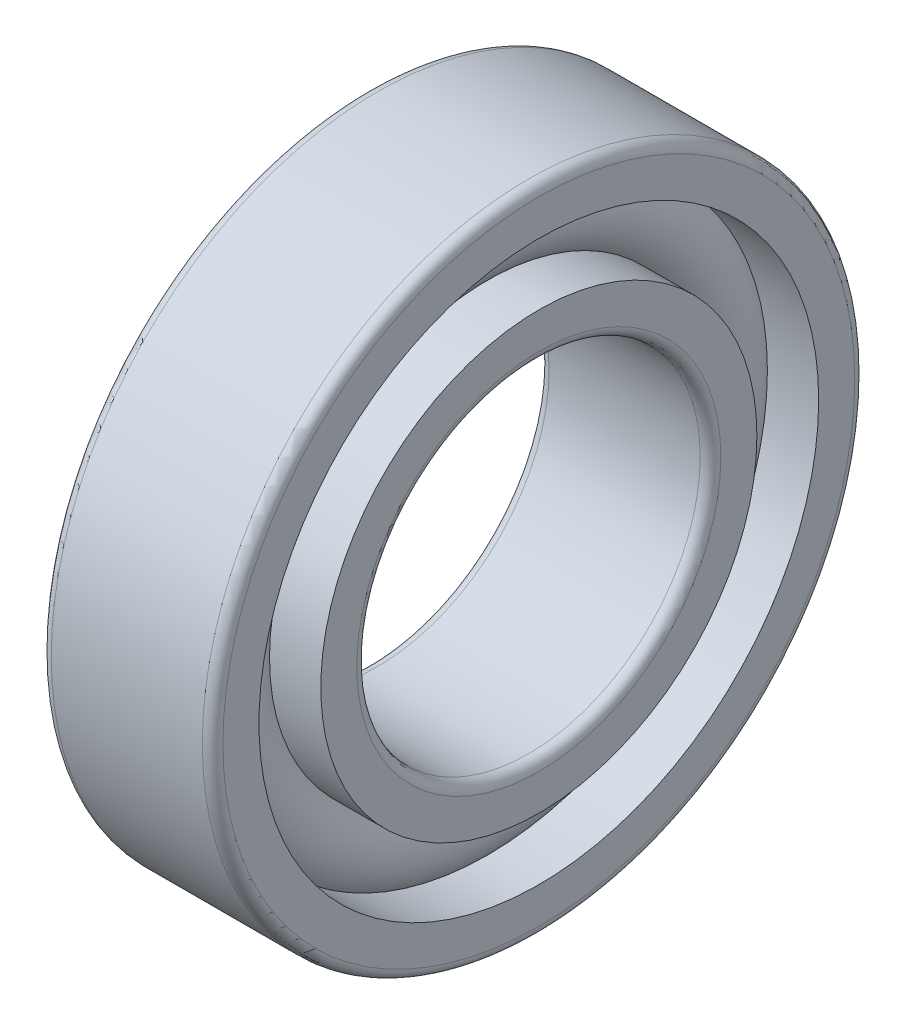
SolidWorks part; units mm, degrees
ref_plane "Plane1" through (0, 0, 0) normal (0, 0, 1) x (1, 0, 0)
ref_plane "Plane2" through (0, 0, 0) normal (0, 1, 0) x (1, 0, 0)
ref_plane "Plane3" through (0, 0, 0) normal (1, 0, 0) x (0, 0, -1)
other "Configuration Table"
sketch "Clipboard" plane through (0, 0, 0) normal (0, 0, 1) x (1, 0, 0)
  line L0 (-10, 0) -> (10, 0) construction
  line L1 (0, 0) -> (22.3471, -0.7804)
  line L2 (0, 0) -> (7.2456, 0.253)
  line L3 (0, 0) -> (22.3471, -0.7804)
  line L4 (0, 0) -> (-22.3573, -0.3902)
  dimension "BallCLRad" = 7.25
sketch "CagSpiSke" plane through (0, 0, 0) normal (0, 0, 1) x (1, 0, 0)
  line L0 (0.135, 7.025) -> (0.135, 7.475)
  line L1 (0.135, 7.475) -> (-0.135, 7.475)
  line L2 (-0.135, 7.475) -> (-0.135, 7.025)
  line L3 (-0.135, 7.025) -> (0.135, 7.025)
  line L4 (-20.6375, 0) -> (20.6375, 0) construction
  line L5 (0, 0) -> (0, 23.7692) construction
  dimension "OD" = 14.95
  dimension "ID" = 14.05
revolve "CageSpine" add sketch "CagSpiSke" angle 0.001 about L4 reverse direction yes
ref_axis "Axis1" through (-50, 0, 0) along (1, 0, 0)
sketch "CagBalSke" plane through (0, 0, 0) normal (0, 0, 1) x (1, 0, 0)
  line L0 (-1.485, 7.25) -> (1.485, 7.25)
  line L1 (-1.905, 7.25) -> (1.905, 7.25) construction
  line L2 (-10, 0) -> (10, 0) construction
  line L3 (0, 0) -> (0, 24) construction
  arc A0 (1.485, 7.25) -> (-1.485, 7.25) centre (0, 7.25) cw
  dimension "BallCLRad" = 7.25
revolve "CageBall" [suppressed] add sketch "CagBalSke" angle 360 about L1 reverse direction yes
pattern_circular "CageBalls" [suppressed] count 2 every 180 about axis through (-50, 0, 0) along (1, 0, 0)
sketch "CagTrmODSke" plane through (0, 0, 0) normal (0, 0, 1) x (1, 0, 0)
  line L0 (1.486, 7.475) -> (1.486, 8.736)
  line L1 (1.486, 8.736) -> (-1.486, 8.736)
  line L2 (-1.486, 8.736) -> (-1.486, 7.475)
  line L3 (-1.486, 7.475) -> (1.486, 7.475)
  line L4 (-20.6375, 0) -> (20.6375, 0) construction
  line L5 (0, 0) -> (0, 25) construction
  dimension "Width" = 2.972
  dimension "ID" = 14.95
  dimension "OD" = 17.472
revolve "CageTrimOD" [suppressed] cut sketch "CagTrmODSke" angle 360 about L4 reverse direction yes
sketch "CagTrmIDSke" plane through (0, 0, 0) normal (0, 0, 1) x (1, 0, 0)
  line L0 (1.486, 5.766) -> (1.486, 7.025)
  line L1 (1.486, 7.025) -> (-1.486, 7.025)
  line L2 (-1.486, 7.025) -> (-1.486, 5.766)
  line L3 (-1.486, 5.766) -> (1.486, 5.766)
  line L4 (-20.6375, 0) -> (20.6375, 0) construction
  line L5 (0, 0) -> (0, 25) construction
  dimension "Width" = 2.972
  dimension "ID" = 11.532
  dimension "OD" = 14.05
revolve "CageTrimID" [suppressed] cut sketch "CagTrmIDSke" angle 360 about L4 reverse direction yes
sketch "BalSimSke" plane through (0, 0, 0) normal (0, 0, 1) x (1, 0, 0)
  line L0 (-10, 0) -> (10, 0) construction
  line L1 (-10, 7.25) -> (10, 7.25) construction
  line L2 (0, 0) -> (0, 23) construction
  circle A0 centre (0, 7.25) radius 1.35
  dimension "BallCLRad" = 7.25
  dimension "Ball_diameter" = 2.7
revolve "BallsSimplified" add sketch "BalSimSke" angle 360 about L0
sketch "BalDetSke" plane through (0, 0, 0) normal (0, 0, 1) x (1, 0, 0)
  line L0 (-1.35, 7.25) -> (1.35, 7.25)
  line L1 (-1.905, 7.25) -> (1.905, 7.25) construction
  line L2 (0, 0) -> (0, 25) construction
  arc A0 (1.35, 7.25) -> (-1.35, 7.25) centre (0, 7.25) cw
  dimension "BallCLRad" = 7.25
  dimension "Ball_diameter" = 2.7
revolve "BallDetailed" [suppressed] add sketch "BalDetSke" angle 360 about L1 reverse direction yes
sketch "InnRacSke" plane through (0, 0, 0) normal (0, 0, 1) x (1, 0, 0)
  line L0 (-0.9724, 6.35) -> (-2.5, 6.35)
  line L1 (-2.5, 6.35) -> (-2.5, 5.3)
  line L2 (-2.2, 5) -> (2.2, 5)
  line L3 (2.5, 5.3) -> (2.5, 6.35)
  line L4 (2.5, 6.35) -> (0.9724, 6.35)
  line L5 (-20.6375, 0) -> (20.6375, 0) construction
  line L6 (0, 0) -> (0, 30) construction
  arc A0 (-2.5, 5.3) -> (-2.2, 5) centre (-2.2, 5.3) ccw
  arc A1 (2.2, 5) -> (2.5, 5.3) centre (2.2, 5.3) ccw
  arc A2 (0.9724, 6.35) -> (-0.9724, 6.35) centre (0, 7.25) cw
  dimension "BallCLRad" = 7.25
  dimension "Fillet_radius" = 0.3
  dimension "Ball_diameter" = 2.65
  dimension "ID" = 10
  dimension "OD" = 12.7
  dimension "Width" = 5
revolve "InnerRace" add sketch "InnRacSke" angle 360 about L5 reverse direction yes
sketch "OutRacSke" plane through (0, 0, 0) normal (0, 0, 1) x (1, 0, 0)
  line L0 (-0.9724, 8.15) -> (-2.5, 8.15)
  line L1 (-2.5, 8.15) -> (-2.5, 9.2)
  line L2 (-2.2, 9.5) -> (2.2, 9.5)
  line L3 (2.5, 9.2) -> (2.5, 8.15)
  line L4 (2.5, 8.15) -> (0.9724, 8.15)
  line L5 (-20.6375, 0) -> (20.6375, 0) construction
  line L6 (0, 0) -> (0, 30) construction
  arc A0 (-2.5, 9.2) -> (-2.2, 9.5) centre (-2.2, 9.2) cw
  arc A1 (2.2, 9.5) -> (2.5, 9.2) centre (2.2, 9.2) cw
  arc A2 (0.9724, 8.15) -> (-0.9724, 8.15) centre (0, 7.25) ccw
  dimension "BallCLRad" = 7.25
  dimension "Fillet_radius" = 0.3
  dimension "Ball_diameter" = 2.65
  dimension "Width" = 5
revolve "OuterRace" add sketch "OutRacSke" angle 360 about L5 reverse direction yes
pattern_circular "BallsDetailed" [suppressed] count 2 every 180 about axis through (-50, 0, 0) along (1, 0, 0)
equation "\"BallCLRad@Clipboard\" = ( \"OD@OutRacSke\" + \"ID@InnRacSke\" ) / 4"
equation "\"BallCLRad@BalSimSke\" = \"BallCLRad@Clipboard\""
equation "\"BallCLRad@BalDetSke\" = \"BallCLRad@Clipboard\""
equation "\"BallCLRad@InnRacSke\" = \"BallCLRad@Clipboard\""
equation "\"BallCLRad@OutRacSke\" = \"BallCLRad@Clipboard\""
equation "\"Ball_diameter@InnRacSke\" = \"Ball_diameter@BalDetSke\" - 0.05"
equation "\"Ball_diameter@OutRacSke\" = \"Ball_diameter@BalDetSke\" - 0.05"
equation "\"Ball_diameter@BalSimSke\" = \"Ball_diameter@BalDetSke\""
equation "\"Width@OutRacSke\" = \"Width@InnRacSke\""
equation "\"Fillet_radius@OutRacSke\" = \"Fillet_radius@InnRacSke\""
equation "\"Max_count@Clipboard\" = int( 3.14159265 / atn(( \"Ball_diameter@BalDetSke\" / 2) / sqr( \"BallCLRad@Clipboard\"  *  \"BallCLRad@Clipboard\" - ( \"Ball_diameter@BalDetSke\" / 2) *  ( \"Ball_diameter@BalDetSke\" / 2))))"
equation "\"Max_count@Clipboard\" = ((sgn( \"Max_count@Clipboard\" - \"Count@Clipboard\" )-1)*( \"Max_count@Clipboard\" - \"Count@Clipboard\" ))/-2+ \"Count@Clipboard\""
equation "\"Count@BallsDetailed\" = int( \"Show_count@Clipboard\" ) "
equation "\"Count@BallsDetailed\" = ((sgn( \"Count@BallsDetailed\" - \"Max_count@Clipboard\" )-1)*( \"Count@BallsDetailed\" - \"Max_count@Clipboard\" ))/-2+ \"Max_count@Clipboard\""
equation "\"Count@BallsDetailed\" = ((sgn( \"Count@BallsDetailed\" - \"Min_count@Clipboard\" )+1)*( \"Count@BallsDetailed\" - \"Min_count@Clipboard\"))/2 +\"Min_count@Clipboard\""
equation "\"Angle@BallsDetailed\" = 360.0 / \"Max_count@Clipboard\""
equation "\"BallCLRad@CagBalSke\" = \"BallCLRad@Clipboard\""
equation "\"Count@CageBalls\" = \"Count@BallsDetailed\""
equation "\"Angle@CageBalls\" = \"Angle@BallsDetailed\""
equation "\"Angle@CageSpine\" =  \"Angle@CageBalls\" * ( \"Count@CageBalls\" -1 + int( \"Count@CageBalls\" / \"Max_count@Clipboard\" ) )  + 0.001 -  int( \"Count@CageBalls\" / \"Max_count@Clipboard\" ) * 0.001"
equation "\"Angle@CageSpine\" =  \"Angle@CageSpine\" * int( \"Min_count@Clipboard\" / 2) + int(1 / \"Min_count@Clipboard\")  * 0.001"
equation "\"CageWallOD@CagBalSke\" =  \"Ball_diameter@BalDetSke\" * 1.1"
equation "\"Thickness@CagSpiSke\" =  \"Ball_diameter@BalDetSke\" * 0.1"
equation "\"OD@CagTrmODSke\" = \"BallCLRad@Clipboard\" * 2 + \"CageWallOD@CagBalSke\" + 0.002"
equation "\"ID@CagTrmODSke\" = \"BallCLRad@Clipboard\" * 2 + \"Ball_diameter@BalDetSke\" / 6"
equation "\"OD@CagTrmIDSke\" = \"BallCLRad@Clipboard\" * 2 - \"Ball_diameter@BalDetSke\" / 6"
equation "\"ID@CagTrmIDSke\" = \"BallCLRad@Clipboard\" * 2 - \"CageWallOD@CagBalSke\" + 0.002"
equation "\"OD@CagSpiSke\" = \"ID@CagTrmODSke\""
equation "\"ID@CagSpiSke\" = \"OD@CagTrmIDSke\""
equation "\"Width@CagTrmODSke\" = \"CageWallOD@CagBalSke\" + 0.002"
equation "\"Width@CagTrmIDSke\" = \"CageWallOD@CagBalSke\" + 0.002"
